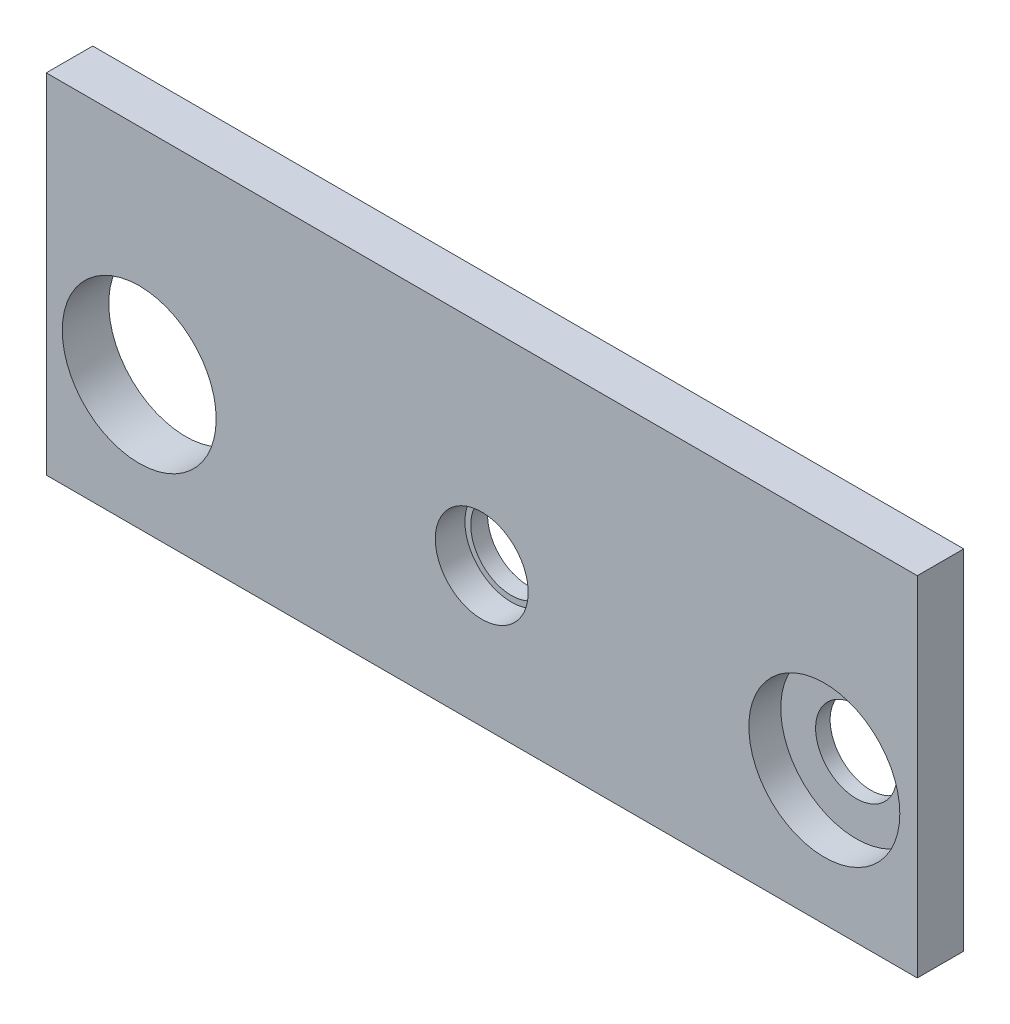
SolidWorks part; units mm, degrees
ref_plane "Front" through (0, 0, 0) normal (0, 0, 1) x (1, 0, 0)
ref_plane "Top" through (0, 0, 0) normal (0, 1, 0) x (1, 0, 0)
ref_plane "Right" through (0, 0, 0) normal (1, 0, 0) x (0, 0, -1)
sketch "Esquisse1" plane through (0, 0, 0) normal (0, 0, 1) x (1, 0, 0)
  line L1 (0, 0) -> (150, 0)
  line L2 (0, 0) -> (0, 60)
  line L3 (0, 60) -> (150, 60)
  line L4 (150, 0) -> (150, 60)
  dimension "D1" = 150
  dimension "D2" = 60
extrude "Boss.-Extru.1" add sketch "Esquisse1" along normal blind 8
sketch "Esquisse2" plane through (0, 0, 8) normal (0, 0, 1) x (1, 0, 0)
  line L0 (75, 0) -> (75, 24) construction
  line L1 (0, 0) -> (150, 0) construction
  circle A0 centre (75, 24) radius 8
  dimension "D1" = 16
  dimension "D2" = 24
extrude "Enlèv. mat.-Extru.1" cut sketch "Esquisse2" against normal blind 5.1 and the other way through all
sketch "Esquisse3" plane through (0, 0, 2.9) normal (0, 0, 1) x (1, 0, 0)
  circle A0 centre (75, 24) radius 7
  dimension "D1" = 14
extrude "Enlèv. mat.-Extru.2" cut sketch "Esquisse3" against normal through all
sketch "Esquisse4" plane through (0, 0, 8) normal (0, 0, 1) x (1, 0, 0)
  line L0 (133.9915, 23) -> (75, 24) construction
  line L1 (0, 0) -> (150, 0) construction
  circle A0 centre (133.9915, 23) radius 7
  point P2 (123.6311, 18.9264)
  dimension "D2" = 23
  dimension "D3" = 14
  dimension "D1" = 59
extrude "Enlèv. mat.-Extru.3" cut sketch "Esquisse4" against normal through all
sketch "Esquisse5" plane through (0, 0, 8) normal (0, 0, 1) x (1, 0, 0)
  circle A0 centre (133.9915, 23) radius 13
  dimension "D1" = 26
extrude "Enlèv. mat.-Extru.4" cut sketch "Esquisse5" against normal blind 5.5
sketch "Esquisse6" plane through (0, 0, 8) normal (0, 0, 1) x (1, 0, 0)
  line L0 (75, 0) -> (75, 60) construction
  line L1 (0, 0) -> (150, 0) construction
  line L2 (150, 60) -> (0, 60) construction
  line L3 (75, 24) -> (16.0085, 23) construction
  line L4 (133.9915, 23) -> (75, 23) construction
  line L5 (75, 23) -> (16.0085, 23) construction
  circle A0 centre (16.0085, 23) radius 13.25
  dimension "D2" = 26.5
  dimension "D1" = 59
extrude "Enlèv. mat.-Extru.5" cut sketch "Esquisse6" against normal through all both and the other way through all
